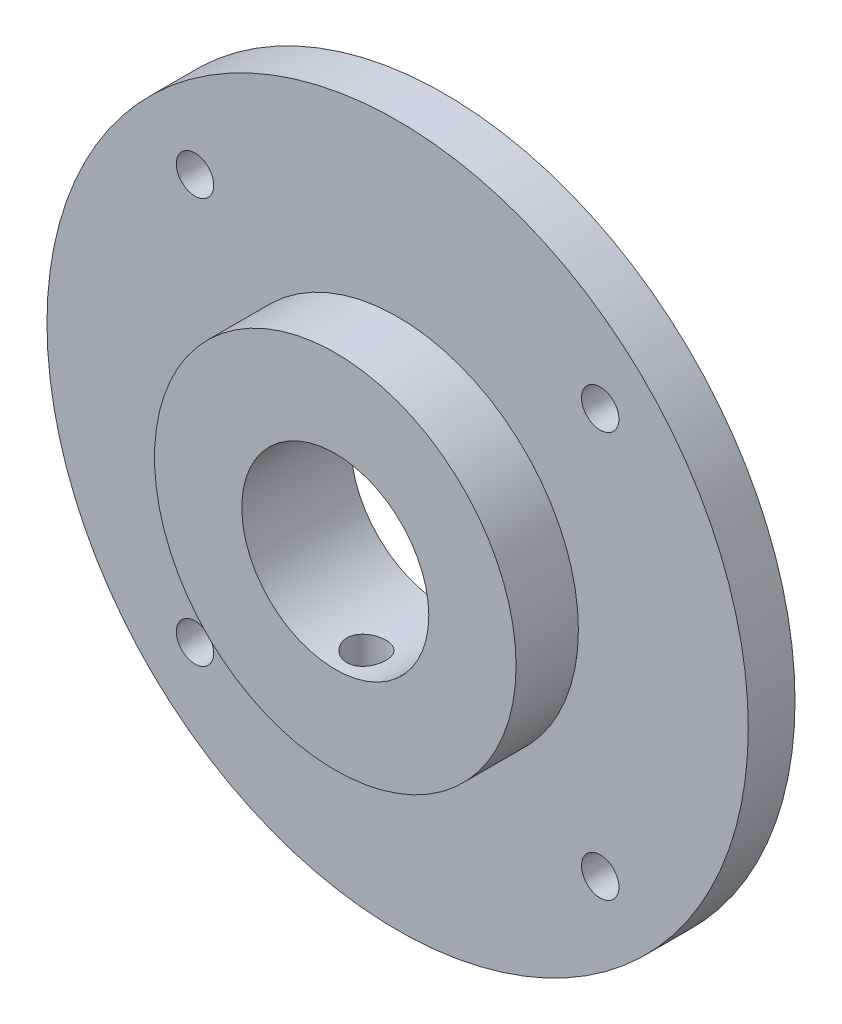
SolidWorks part; units mm, degrees
ref_plane "前视基准面" through (0, 0, 0) normal (0, 0, 1) x (1, 0, 0)
ref_plane "上视基准面" through (0, 0, 0) normal (0, 1, 0) x (1, 0, 0)
ref_plane "右视基准面" through (0, 0, 0) normal (1, 0, 0) x (0, 0, -1)
other "Configuration Table"
sketch "草图1" plane through (0, 0, 0) normal (0, 0, 1) x (1, 0, 0)
  line L8 (-44.55, -13.5) -> (-3.1668, -13.5)
  line L9 (5.45, -15) -> (5.45, -32.5)
  line L10 (5.45, -32.5) -> (100, -32.5)
  line L11 (100, -32.5) -> (100, 34.5)
  line L12 (100, 34.5) -> (-100, 34.5)
  line L13 (-100, 34.5) -> (-100, 5)
  line L14 (-100, 5) -> (-44.55, 5)
  line L15 (-44.55, 5) -> (-44.55, -13.5)
  line L16 (-44.55, -13.5) -> (-3.1668, -13.5)
  line L17 (5.45, -15) -> (5.45, -32.5)
  line L18 (5.45, -32.5) -> (100, -32.5)
  line L19 (100, -32.5) -> (100, 34.5)
  line L20 (100, 34.5) -> (-100, 34.5)
  line L21 (-100, 34.5) -> (-100, 5)
  line L22 (-100, 5) -> (-44.55, 5)
  line L23 (-44.55, 5) -> (-44.55, -13.5)
  circle A0 centre (5.45, 10.5) radius 22.5 construction
  arc A1 (-3.1668, -13.5) -> (5.45, -15) centre (5.45, 10.5) ccw
  arc A2 (-3.1668, -13.5) -> (5.45, -15) centre (5.45, 10.5) ccw
  circle A3 centre (5.45, 10.5) radius 22.5
  circle A4 centre (18.45, -2.5) radius 1.2 construction
  circle A5 centre (18.45, -2.5) radius 1.2
  circle A6 centre (18.45, 23.5) radius 1.2 construction
  circle A7 centre (18.45, 23.5) radius 1.2
  circle A8 centre (-7.55, 23.5) radius 1.2 construction
  circle A9 centre (-7.55, 23.5) radius 1.2
  circle A10 centre (-7.55, -2.5) radius 1.2 construction
  circle A11 centre (-7.55, -2.5) radius 1.2
  circle A12 centre (5.45, 10.5) radius 6
  dimension "D2" = 12
  dimension "D1" = 0
extrude "凸台-拉伸1" add sketch "草图1" along normal blind 3 contours A3 A12 A11 A9 A7 A5 region at (-16.4136, 10.5, 0)
sketch "草图3" plane through (0, 0, 3) normal (0, 0, 1) x (1, 0, 0)
  circle A0 centre (5.45, 10.5) radius 6 construction
  circle A1 centre (5.45, 10.5) radius 22.5
  circle A2 centre (5.45, 10.5) radius 22.5
  circle A3 centre (5.45, 10.5) radius 6
  circle A4 centre (5.45, 10.5) radius 7.6
  circle A5 centre (5.45, 10.5) radius 11.6
  dimension "D2" = 15.2
  dimension "D1" = 0
  dimension "D3" = 4
extrude "凸台-拉伸2" add sketch "草图3" along normal blind 4.2 contours A5 A4 region at (-5.8219, 10.5, 3)
sketch "草图4" plane through (0, 0, 7.2) normal (0, 0, 1) x (1, 0, 0)
  circle A1 centre (5.45, 10.5) radius 11.6
  circle A2 centre (5.45, 10.5) radius 11.6
  dimension "D1" = 0
extrude "切除-拉伸1" cut sketch "草图4" against normal blind 0.2
sketch "草图5" plane through (0, 0, 3) normal (0, 0, 1) x (1, 0, 0)
  circle A0 centre (5.45, 10.5) radius 6 construction
  circle A1 centre (5.45, 10.5) radius 7.6
  circle A2 centre (5.45, 10.5) radius 7.6
  circle A3 centre (5.45, 10.5) radius 6
  dimension "D1" = 0
extrude "凸台-拉伸3" add sketch "草图5" along normal up to surface (4 mm away) contours A2 | A3 up to face at (13.05, 10.5, 7)
sketch "草图6" plane through (0, 0, 0) normal (0, 1, 0) x (1, 0, 0)
  line L0 (-6.15, -3) -> (17.05, -7)
  line L1 (-6.15, -7) -> (17.05, -7)
  line L2 (-6.15, -7) -> (-6.15, -3)
  line L3 (-6.15, -3) -> (17.05, -3)
  line L4 (17.05, -7) -> (17.05, -3)
  circle A0 centre (5.45, -5) radius 1.25
  dimension "D1" = 2.5
extrude "切除-拉伸2" cut sketch "草图6" along normal blind 10 and the other way blind 10 contours L0 A0 | L0 A0 region at (5.5401, 0, 4.4772) region at (5.3599, 0, 5.5228)
